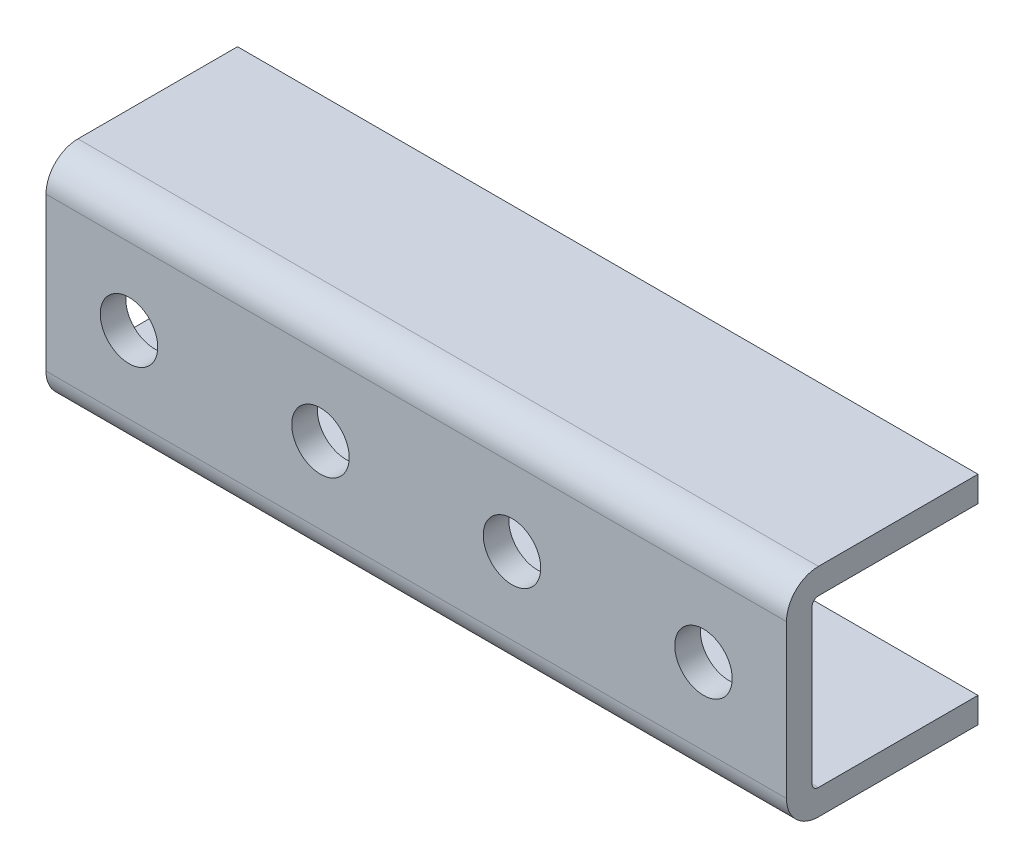
SolidWorks part; units mm, degrees
ref_plane "Front Plane" through (0, 0, 0) normal (0, 0, 1) x (1, 0, 0)
ref_plane "Top Plane" through (0, 0, 0) normal (0, 1, 0) x (1, 0, 0)
ref_plane "Right Plane" through (0, 0, 0) normal (1, 0, 0) x (0, 0, -1)
sketch "Sketch1" plane through (0, 0, 0) normal (0, 0, 1) x (1, 0, 0)
  line L0 (-92.075, 0) -> (92.075, 0) construction
  line L1 (-92.075, 26.9875) -> (92.075, 26.9875)
  line L2 (-92.075, 26.9875) -> (-92.075, -26.9875)
  line L3 (-92.075, -26.9875) -> (92.075, -26.9875)
  line L4 (92.075, 26.9875) -> (92.075, -26.9875)
  line L5 (0, 20.6375) -> (0, -20.6375) construction
  dimension "D1" = 53.975
  dimension "A" = 184.15
  dimension "B" = 41.275
extrude "Boss-Extrude1" add sketch "Sketch1" along normal mid plane 47.625
fillet "Fillet1" radius 7.9375 2 edges at (0, -26.9875, 23.8125) (0, 26.9875, 23.8125)
shell "Shell1" thickness 6.35 removed face at (-92.075, 0, 5.8396) removed face at (92.075, 0, 5.8396) removed face at (0, 0, -23.8125)
sketch "Sketch2" plane through (0, 0, 23.8125) normal (0, 0, 1) x (1, 0, 0)
  line L0 (-92.075, 0) -> (92.075, 0) construction
  line L1 (-92.075, 19.05) -> (-92.075, -19.05) construction
  line L2 (92.075, -19.05) -> (92.075, 19.05) construction
  circle A0 centre (-71.4375, 0) radius 7.1438
  circle A1 centre (-23.8125, 0) radius 7.1438
  circle A2 centre (23.8125, 0) radius 7.1438
  circle A3 centre (71.4375, 0) radius 7.1438
  dimension "Hole Size" = 14.2875
  dimension "Spacing" = 47.625
  dimension "D3" = 47.625
  dimension "D4" = 47.625
  dimension "D5" = 23.8125
extrude "Cut-Extrude1" cut sketch "Sketch2" against normal blind 47.625
equation "\"D1@Sketch1\" = (\"Thickness@Shell1\"*2)+1.625"
equation "\"D1@Boss-Extrude1\" = \"B@Sketch1\"+\"Thickness@Shell1\""
equation "\"D4@Sketch2\" = \"Spacing@Sketch2\""
equation "\"D3@Sketch2\" = \"Spacing@Sketch2\""
equation "\"D5@Sketch2\" = \"Spacing@Sketch2\"/2"
